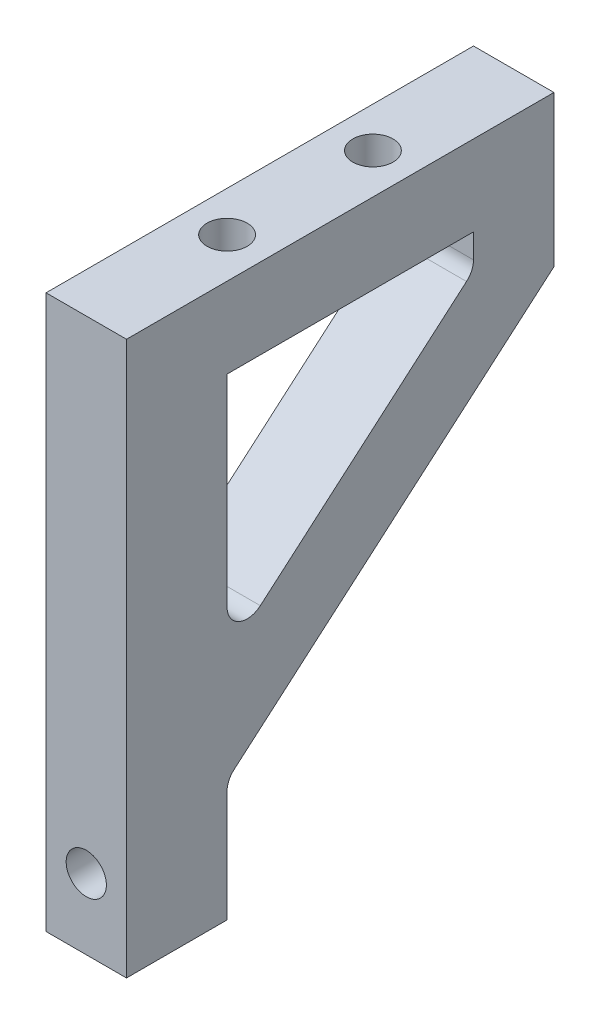
SolidWorks part; units mm, degrees
ref_plane "前视基准面" through (0, 0, 0) normal (0, 0, 1) x (1, 0, 0)
ref_plane "上视基准面" through (0, 0, 0) normal (0, 1, 0) x (1, 0, 0)
ref_plane "右视基准面" through (0, 0, 0) normal (1, 0, 0) x (0, 0, -1)
sketch "草图1" plane through (0, 0, 0) normal (1, 0, 0) x (0, 0, -1)
  line L0 (0, 0) -> (42.5, 0)
  line L1 (42.5, 0) -> (42.5, -15)
  line L3 (10, -55) -> (0, -55)
  line L4 (0, -55) -> (0, 0)
  line L12 (42.5, -15) -> (10, -43)
  line L13 (10, -43) -> (10, -55)
  line L14 (10, -32.4405) -> (34.5, -11.3328)
  line L15 (34.5, -11.3328) -> (34.5, -8)
  line L16 (34.5, -8) -> (10, -8)
  line L17 (10, -8) -> (10, -32.4405)
  dimension "D1" = 42.5
  dimension "D2" = 10
  dimension "D3" = 40
  dimension "D4" = 55
  dimension "D8" = 12
  dimension "D9" = 8
  dimension "D10" = 8
  dimension "D11" = 8
extrude "凸台-拉伸1" add sketch "草图1" along normal mid plane 8
sketch "草图2" plane through (0, 0, 0) normal (0, 1, 0) x (1, 0, 0)
  line L0 (4, 42.5) -> (-4, 42.5) construction
  circle A0 centre (0, 14) radius 2
  circle A1 centre (0, 28.5) radius 2
  dimension "D1" = 4
  dimension "D2" = 14
  dimension "D3" = 14
extrude "切除-拉伸1" cut sketch "草图2" against normal up to next
sketch "草图4" plane through (0, 0, -10) normal (0, 0, -1) x (-1, 0, 0)
  line L0 (-4, -55) -> (4, -55) construction
  circle A0 centre (0, -48) radius 2
  point P4 (0, -55)
  dimension "D1" = 4
  dimension "D2" = 7
  dimension "D3" = 7
extrude "切除-拉伸3" cut sketch "草图4" against normal up to next
fillet "圆角1" radius 2 3 edges at (0, -11.3328, -34.5) (0, -43, -10) (0, -32.4405, -10)
chamfer "倒角1" distance 2 angle 45 1 edges at (0, -46, -10)
